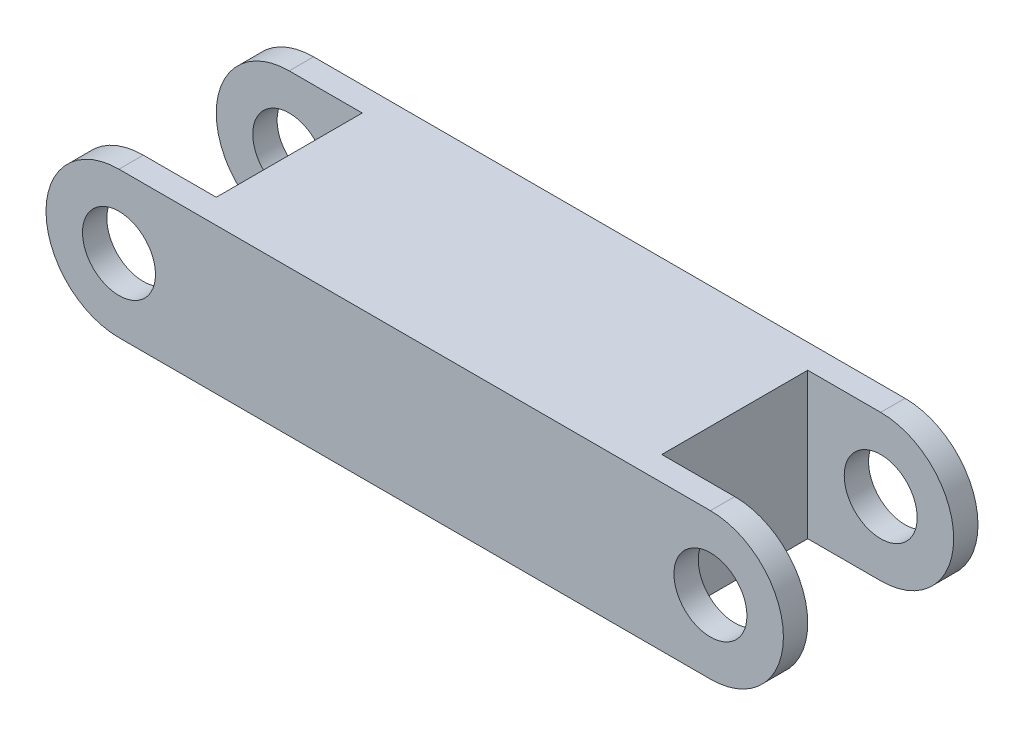
SolidWorks part; units mm, degrees
ref_plane "Front Plane" through (0, 0, 0) normal (0, 0, 1) x (1, 0, 0)
ref_plane "Top Plane" through (0, 0, 0) normal (0, 1, 0) x (1, 0, 0)
ref_plane "Right Plane" through (0, 0, 0) normal (1, 0, 0) x (0, 0, -1)
sketch "Sketch1" plane through (0, 0, 0) normal (0, 0, 1) x (1, 0, 0)
  line L0 (0, 0) -> (121.5798, 0) construction
  line L1 (0, 15) -> (121.5798, 15)
  line L2 (0, -15) -> (121.5798, -15)
  arc A0 (0, 15) -> (0, -15) centre (0, 0) ccw
  arc A1 (121.5798, -15) -> (121.5798, 15) centre (121.5798, 0) ccw
  circle A2 centre (0, 0) radius 7.5
  circle A3 centre (121.5798, 0) radius 7.5
  point P3 (60.7899, 0)
  point P12 (107.4399, 0)
  point P13 (160.3623, 0)
  point P14 (121.5798, 0)
  dimension "D1" = 15
  dimension "D2" = 15
  dimension "D3" = 30
extrude "Boss-Extrude1" add sketch "Sketch1" along normal blind 40
sketch "Sketch2" plane through (0, 15, 0) normal (0, 1, 0) x (1, 0, 0)
  line L0 (-15, 0) -> (-15, -40) construction
  line L1 (15, -5) -> (-15, -5)
  line L2 (15, -5) -> (15, -35)
  line L3 (15, -35) -> (-15, -35)
  line L4 (-15, -5) -> (-15, -35)
  line L5 (136.5798, -40) -> (136.5798, 0) construction
  line L6 (0, -40) -> (0, 0) construction
  line L15 (106.5798, -35) -> (136.5798, -35)
  line L16 (106.5798, -35) -> (106.5798, -5)
  line L17 (106.5798, -5) -> (136.5798, -5)
  line L18 (136.5798, -35) -> (136.5798, -5)
  line L19 (121.5798, -40) -> (121.5798, 0) construction
  point P7 (-15, -20)
  point P10 (0, -20)
  point P15 (136.5798, -20)
  point P19 (121.5798, -20)
  dimension "D1" = 30
  dimension "D2" = 30
  dimension "D3" = 30
  dimension "D4" = 30
extrude "Cut-Extrude1" cut sketch "Sketch2" against normal through all
